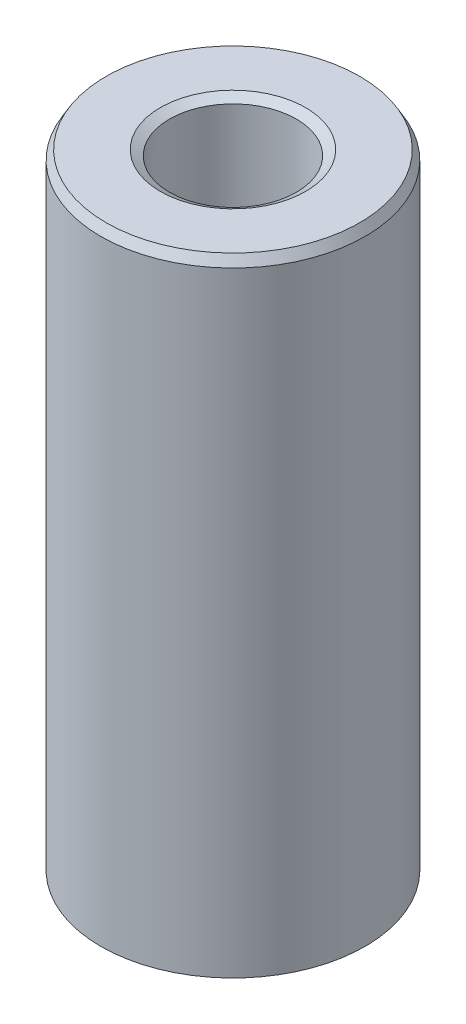
SolidWorks part; units mm, degrees
ref_plane "Front Plane" through (0, 0, 0) normal (0, 0, 1) x (1, 0, 0)
ref_plane "Top Plane" through (0, 0, 0) normal (0, 1, 0) x (1, 0, 0)
ref_plane "Right Plane" through (0, 0, 0) normal (1, 0, 0) x (0, 0, -1)
sketch "Sketch1" plane through (0, 0, 0) normal (0, 1, 0) x (1, 0, 0)
  circle A0 centre (0, 0) radius 35
  dimension "SLEEVE_OD" = 70
extrude "Boss-Extrude1" add sketch "Sketch1" along normal blind 166.7159
sketch "Sketch2" plane through (0, 0, 0) normal (0, 1, 0) x (1, 0, 0)
  circle A0 centre (0, 0) radius 16.8053
  dimension "BORE_D" = 33.6105
extrude "Cut-Extrude1" cut sketch "Sketch2" along normal through all
chamfer "Chamfer1" distance 2.4428 angle 30 4 edges at (0, 166.7159, 16.8053) (0, 0, 16.8053) (0, 0, 35) (0, 166.7159, 35) first distance on face at (0, 166.7159, 16.8053) first distance on face at (0, 0, 16.8053) first distance on face at (0, 166.7159, 35)
